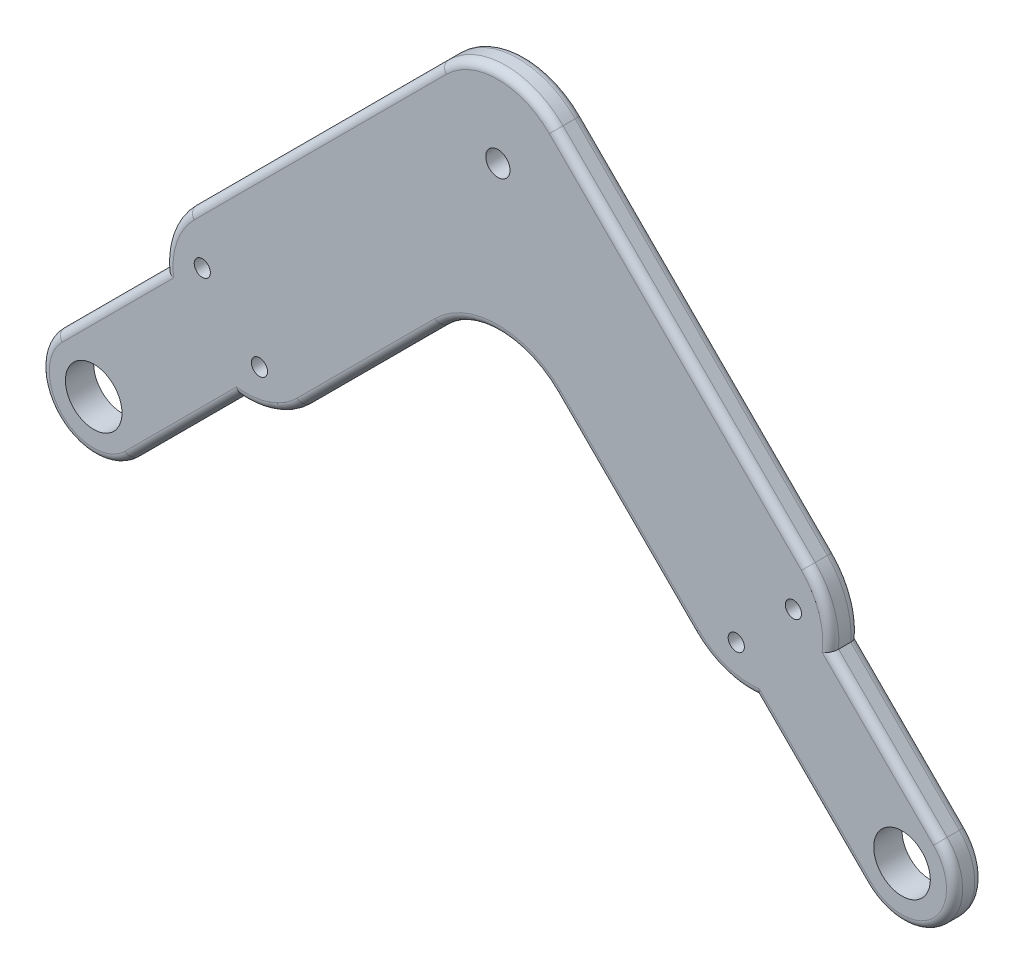
SolidWorks part; units mm, degrees
ref_plane "Front Plane" through (0, 0, 0) normal (0, 0, 1) x (1, 0, 0)
ref_plane "Top Plane" through (0, 0, 0) normal (0, 1, 0) x (1, 0, 0)
ref_plane "Right Plane" through (0, 0, 0) normal (1, 0, 0) x (0, 0, -1)
sketch "Sketch1" plane through (0, 0, 0) normal (0, 0, 1) x (1, 0, 0)
  line L0 (-100, 0) -> (100, 0) construction
  line L1 (-100, 0) -> (0, 100) construction
  line L2 (0, 100) -> (100, 0) construction
  line L3 (0, 0) -> (-50, 50) construction
  line L4 (-40, 60) -> (40, 60) construction
  line L5 (0, 100) -> (0, 60) construction
  circle A0 centre (-100, 0) radius 20
  circle A1 centre (0, 0) radius 20
  circle A2 centre (100, 0) radius 20
  point P2 (0, 0)
  dimension "D5" = 40
  dimension "D1" = 200
  dimension "D2" = 90
  dimension "D3" = 90
  dimension "D4" = 80
sketch "Sketch2" plane through (0, 0, 0) normal (0, 0, 1) x (1, 0, 0)
  line L0 (-56.5165, 43.4835) -> (-40, 60) construction
  line L1 (-100, 0) -> (0, 100) construction
  line L2 (-40, 60) -> (40, 60) construction
  line L3 (40, 60) -> (86.565, 13.435) construction
  line L4 (0, 100) -> (100, 0) construction
  line L5 (-49.4454, 36.4124) -> (-35.8579, 50)
  line L6 (-35.8579, 50) -> (35.8579, 50)
  line L7 (35.8579, 50) -> (79.4939, 6.364)
  line L8 (-63.5876, 50.5546) -> (-44.1421, 70)
  line L9 (-44.1421, 70) -> (44.1421, 70)
  line L10 (44.1421, 70) -> (93.636, 20.5061)
  line L11 (-63.5876, 50.5546) -> (-49.4454, 36.4124)
  line L12 (93.636, 20.5061) -> (79.4939, 6.364)
  line L13 (81.9688, 8.8388) -> (95.4038, -4.5962)
  line L14 (91.1612, 18.0312) -> (104.5962, 4.5962)
  line L15 (90.1005, 24.0416) -> (75.9584, 9.8995) construction
  line L16 (0, 100) -> (0, 60) construction
  line L17 (-6, 70) -> (-3.4532, 85.4203)
  line L18 (6, 70) -> (3.4532, 85.4203)
  circle A0 centre (100, 0) radius 10 construction
  circle A1 centre (100, 0) radius 3.5
  arc A2 (95.4038, -4.5962) -> (104.5962, 4.5962) centre (100, 0) ccw
  circle A3 centre (100, 0) radius 0.5
  circle A4 centre (100, 0) radius 6.5 construction
  circle A5 centre (79.4939, 13.435) radius 1
  circle A6 centre (86.565, 20.5061) radius 1
  circle A7 centre (0, 60) radius 1.5
  circle A8 centre (0, 84.85) radius 1.5
  circle A9 centre (0, 84.85) radius 3.5
  circle A10 centre (-50, 50) radius 1.5
  dimension "D4" = 20
  dimension "D5" = 7
  dimension "D12" = 2
  dimension "D13" = 3
  dimension "D18" = 3
  dimension "D3" = 27.5
  dimension "D8" = 19
  dimension "D9" = 5
  dimension "D10" = 5
  dimension "D11" = 5
  dimension "D14" = 14.85
  dimension "D16" = 6
  dimension "D17" = 6
  dimension "D1" = 10
  dimension "D2" = 10
  dimension "D6" = 3
  dimension "D7" = 3
  dimension "D15" = 2
sketch "Sketch3" plane through (0, 0, 0) normal (0, 0, 1) x (1, 0, 0)
  line L0 (-100, 0) -> (100, 0) construction
  line L1 (-86.565, 13.435) -> (-50, 50) construction
  line L2 (-100, 0) -> (0, 100) construction
  line L3 (-50, 50) -> (-13.435, 13.435) construction
  line L4 (0, 0) -> (-50, 50) construction
  line L5 (-79.4939, 6.364) -> (-50, 35.8579)
  line L6 (-50, 35.8579) -> (-20.5061, 6.364)
  line L7 (-93.636, 20.5061) -> (-50, 64.1421)
  line L8 (-50, 64.1421) -> (-6.364, 20.5061)
  line L9 (-93.636, 20.5061) -> (-79.4939, 6.364)
  line L10 (-20.5061, 6.364) -> (-6.364, 20.5061)
  line L11 (-91.1612, 18.0312) -> (-104.5962, 4.5962)
  line L12 (-81.9688, 8.8388) -> (-95.4038, -4.5962)
  line L13 (-18.0312, 8.8388) -> (-4.5962, -4.5962)
  line L14 (-8.8388, 18.0312) -> (4.5962, 4.5962)
  line L15 (-90.1005, 24.0416) -> (-75.9584, 9.8995) construction
  line L16 (-9.8995, 24.0416) -> (-24.0416, 9.8995) construction
  circle A0 centre (-100, 0) radius 3.5
  circle A1 centre (0, 0) radius 3.5
  circle A2 centre (-100, 0) radius 10 construction
  circle A3 centre (0, 0) radius 10 construction
  circle A4 centre (-100, 0) radius 6.5
  circle A5 centre (0, 0) radius 6.5
  circle A6 centre (-86.565, 20.5061) radius 1
  circle A7 centre (-79.4939, 13.435) radius 1
  circle A8 centre (-20.5061, 13.435) radius 1
  circle A9 centre (-13.435, 20.5061) radius 1
  circle A10 centre (-50, 50) radius 1.5 construction
  circle A11 centre (-50, 50) radius 1.5
  dimension "D1" = 20
  dimension "D2" = 7
  dimension "D8" = 2
  dimension "D11" = 5
  dimension "D12" = 5
  dimension "D13" = 5
  dimension "D14" = 5
  dimension "D6" = 19
  dimension "D7" = 19
  dimension "D9" = 5
  dimension "D10" = 5
  dimension "D3" = 3
  dimension "D4" = 10
  dimension "D5" = 10
sketch "Sketch4" plane through (0, 0, 0) normal (0, 0, 1) x (1, 0, 0)
  line L0 (-44.1421, 70) -> (44.1421, 70)
  line L1 (44.1421, 70) -> (57.5, 84.85)
  line L2 (57.5, 84.85) -> (57.5, 94.85)
  line L3 (57.5, 94.85) -> (-57.5, 94.85)
  line L4 (-57.5, 94.85) -> (-57.5, 84.85)
  line L5 (-57.5, 84.85) -> (-44.1421, 70)
  line L6 (-4, 60) -> (-4, 70)
  line L7 (4, 60) -> (4, 70)
  line L8 (-22.5, 86.35) -> (22.5, 86.35) construction
  line L9 (-22.5, 90.85) -> (22.5, 90.85)
  line L10 (-22.5, 81.85) -> (22.5, 81.85)
  circle A0 centre (0, 60) radius 1.5 construction
  circle A1 centre (0, 60) radius 1.5
  arc A2 (-4, 60) -> (4, 60) centre (0, 60) ccw
  circle A3 centre (0, 60) radius 4 construction
  arc A4 (-22.5, 90.85) -> (-22.5, 81.85) centre (-22.5, 86.35) ccw
  arc A5 (22.5, 81.85) -> (22.5, 90.85) centre (22.5, 86.35) ccw
  point P4 (0, 94.85)
  point P22 (0, 86.35)
  dimension "D1" = 115
  dimension "D2" = 10
  dimension "D3" = 2.5
  dimension "D4" = 45
  dimension "D5" = 9
  dimension "D6" = 4
sketch "Sketch5" plane through (0, 0, 0) normal (0, 0, 1) x (1, 0, 0)
  line L0 (-18.0312, 8.8388) -> (-4.5962, -4.5962) construction
  line L1 (-81.9688, 8.8388) -> (-95.4038, -4.5962) construction
  line L2 (-91.1612, 18.0312) -> (-104.5962, 4.5962) construction
  line L3 (-8.8388, 18.0312) -> (4.5962, 4.5962) construction
  line L4 (-18.0312, 8.8388) -> (-4.5962, -4.5962)
  line L5 (-81.9688, 8.8388) -> (-95.4038, -4.5962)
  line L6 (-79.4939, 6.364) -> (-50, 35.8579)
  line L7 (-50, 35.8579) -> (-20.5061, 6.364)
  line L8 (-20.5061, 6.364) -> (-6.364, 20.5061)
  line L9 (-6.364, 20.5061) -> (-50, 64.1421)
  line L10 (-50, 64.1421) -> (-93.636, 20.5061)
  line L11 (-93.636, 20.5061) -> (-79.4939, 6.364)
  line L12 (-79.4939, 6.364) -> (-50, 35.8579)
  line L13 (-50, 35.8579) -> (-20.5061, 6.364)
  line L14 (-20.5061, 6.364) -> (-18.0312, 8.8388)
  line L15 (-6.364, 20.5061) -> (-50, 64.1421)
  line L16 (-50, 64.1421) -> (-93.636, 20.5061)
  line L17 (-93.636, 20.5061) -> (-91.1612, 18.0312)
  line L18 (-91.1612, 18.0312) -> (-104.5962, 4.5962)
  line L19 (-8.8388, 18.0312) -> (4.5962, 4.5962)
  line L20 (-81.9688, 8.8388) -> (-79.4939, 6.364)
  line L21 (-8.8388, 18.0312) -> (-6.364, 20.5061)
  circle A1 centre (0, 0) radius 6.5
  arc A2 (-4.5962, -4.5962) -> (4.5962, 4.5962) centre (0, 0) ccw
  circle A3 centre (-100, 0) radius 6.5
  arc A4 (-104.5962, 4.5962) -> (-95.4038, -4.5962) centre (-100, 0) ccw
  circle A5 centre (0, 0) radius 3.5
  circle A6 centre (0, 0) radius 3.5
  circle A7 centre (-100, 0) radius 3.5
  circle A8 centre (-100, 0) radius 3.5
  circle A9 centre (-50, 50) radius 1.5
  circle A10 centre (-50, 50) radius 1.5
  circle A11 centre (-13.435, 20.5061) radius 1
  circle A12 centre (-13.435, 20.5061) radius 1
  circle A13 centre (-20.5061, 13.435) radius 1
  circle A14 centre (-20.5061, 13.435) radius 1
  circle A15 centre (-79.4939, 13.435) radius 1
  circle A16 centre (-79.4939, 13.435) radius 1
  circle A17 centre (-86.565, 20.5061) radius 1
  circle A18 centre (-86.565, 20.5061) radius 1
  dimension "D1" = 0
  dimension "D2" = 0
  dimension "D3" = 0
  dimension "D4" = 0
  dimension "D5" = 0
  dimension "D6" = 0
  dimension "D7" = 0
  dimension "D8" = 0
  dimension "D9" = 0
  dimension "D10" = 0
extrude "Boss-Extrude1" add sketch "Sketch5" along normal blind 3.5
fillet "Fillet1" radius 10 6 edges at (-93.636, 20.5061, 1.75) (-79.4939, 6.364, 1.75) (-6.364, 20.5061, 1.75) (-20.5061, 6.364, 1.75) (-50, 35.8579, 1.75) (-50, 64.1421, 1.75)
fillet "Fillet2" radius 1 32 edges at (-9.4279, 22.2732, 0) (-27.3332, 41.4754, 0) (-50, 60, 0) (-90.5721, 22.2732, 0) (-11.3137, 2.1213, 3.5) (4.5962, -4.5962, 3.5) (-9.4279, 22.2732, 3.5) (-27.3332, 41.4754, 3.5) (-50, 60, 3.5) (-90.5721, 22.2732, 3.5) (-2.1213, 11.3137, 0) (4.5962, -4.5962, 0) (-77.7268, 9.4279, 0) (-22.2732, 9.4279, 0) (-34.4043, 20.2622, 0) (-50, 31.7157, 0) (-97.8787, 11.3137, 0) (-104.5962, -4.5962, 0) (-97.8787, 11.3137, 3.5) (-104.5962, -4.5962, 3.5) (-77.7268, 9.4279, 3.5) (-22.2732, 9.4279, 3.5) (-34.4043, 20.2622, 3.5) (-50, 31.7157, 3.5) (-72.6668, 41.4754, 0) (-2.1213, 11.3137, 3.5) (-72.6668, 41.4754, 3.5) (-11.3137, 2.1213, 0) (-65.5957, 20.2622, 0) (-88.6863, 2.1213, 0) (-88.6863, 2.1213, 3.5) (-65.5957, 20.2622, 3.5)
scale "Scale1" scale about centroid uniform scaling yes scale factor 18
